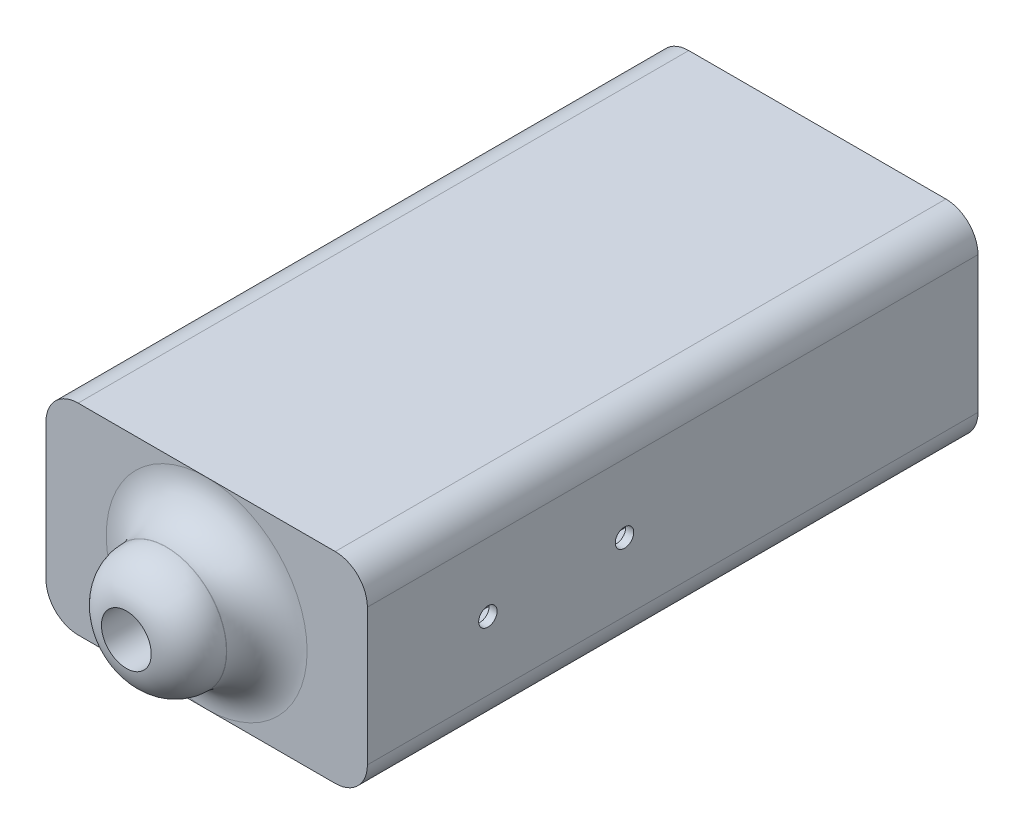
SolidWorks part; units mm, degrees
material "PLA Aero Bambu"
ref_plane "Front Plane" through (0, 0, 0) normal (0, 0, 1) x (1, 0, 0)
ref_plane "Top Plane" through (0, 0, 0) normal (0, 1, 0) x (1, 0, 0)
ref_plane "Right Plane" through (0, 0, 0) normal (1, 0, 0) x (0, 0, -1)
sketch "Sketch1" plane through (0, 0, 0) normal (0, 0, 1) x (1, 0, 0)
  line L1 (-20, 12.5) -> (20, 12.5)
  line L2 (-20, 12.5) -> (-20, -12.5)
  line L3 (-20, -12.5) -> (20, -12.5)
  line L4 (20, 12.5) -> (20, -12.5)
  line L5 (-20, 12.5) -> (20, -12.5) construction
  line L6 (-20, -12.5) -> (20, 12.5) construction
  circle A0 centre (0, 0) radius 2
  point P0 (0, 0)
  dimension "D3" = 4
  dimension "D1" = 25
  dimension "D2" = 40
extrude "Boss-Extrude1" add sketch "Sketch1" against normal blind 1
sketch "Sketch2" plane through (0, 0, -1) normal (0, 0, -1) x (-1, 0, 0)
  line L0 (-20, 12.5) -> (-20, -12.5)
  line L1 (20, -12.5) -> (-20, -12.5) construction
  line L2 (-20, -12.5) -> (20, -12.5)
  line L3 (20, -12.5) -> (20, 12.5)
  line L4 (20, 12.5) -> (-20, 12.5)
  line L5 (19, 11.5) -> (-19, 11.5)
  line L6 (-19, 11.5) -> (-19, -11.5)
  line L7 (-19, -11.5) -> (19, -11.5)
  line L8 (19, -11.5) -> (19, 11.5)
  dimension "D1" = 1
extrude "Boss-Extrude2" add sketch "Sketch2" along normal blind 75
fillet "Fillet2" radius 4 8 edges at (20, 12.5, -38) (20, -12.5, -38) (-20, -12.5, -38) (-20, 12.5, -38) (-19, -11.5, -38.5) (-19, 11.5, -38.5) (19, 11.5, -38.5) (19, -11.5, -38.5)
sketch "Sketch4" plane through (0, 0, 0) normal (0, 0, 1) x (1, 0, 0)
  circle A0 centre (0, 0) radius 7.5
  circle A1 centre (0, 0) radius 3.1
  dimension "D1" = 6.2
  dimension "D2" = 15
extrude "Boss-Extrude3" add sketch "Sketch4" along normal blind 10
fillet "Fillet3" radius 5 2 edges at (7.5, 0, 0) (7.5, 0, 10)
sketch "Sketch5" plane through (20, 0, 0) normal (1, 0, 0) x (0, 0, -1)
  circle A0 centre (15, 0) radius 1.15
  circle A1 centre (32, 0) radius 1.15
  point P5 (30.5, 0)
  point P6 (0, 0)
  dimension "D1" = 2.3
  dimension "D3" = 2.3
  dimension "D2" = 15
  dimension "D4" = 17
extrude "Cut-Extrude1" cut sketch "Sketch5" against normal through all
sketch "Sketch10" plane through (0, -11.5, 0) normal (0, 1, 0) x (1, 0, 0)
  line L0 (-20, 32.5) -> (20, 32.5)
  line L1 (15, 1) -> (-15, 1) construction
  line L2 (20, 30.85) -> (20, 33.15) construction
  line L3 (-15, 76) -> (-15, 1) construction
  line L5 (-20, 33.15) -> (-20, 30.85) construction
  line L6 (-15, 47.6018) -> (7.4768, 47.6018)
  line L7 (-15, 47.6018) -> (-15, 25.1)
  line L8 (-15, 25.1) -> (7.4768, 25.1)
  line L9 (7.4768, 47.6018) -> (7.4768, 25.1)
  point P2 (13.2446, 32.5)
  line B0 (7.4768, 39.9) -> (13.2446, 39.9) construction
  line B1 (-15, 47.6018) -> (7.4768, 47.6018) construction
  line B2 (-15, 47.6018) -> (-15, 25.1) construction
  line B3 (-15, 25.1) -> (7.4768, 25.1) construction
  line B4 (7.4768, 47.6018) -> (7.4768, 25.1) construction
  line B5 (13.2446, 39.9) -> (13.2446, 25.1) construction
  line B6 (13.2446, 25.1) -> (7.4768, 25.1) construction
  line B7 (3.3268, 47.6165) -> (3.3268, 52.475) construction
  line B8 (3.3268, 52.475) -> (5.8268, 52.475) construction
  line B9 (5.8268, 52.475) -> (5.7933, 47.65) construction
  line B10 (5.8268, 25.1) -> (5.8268, 20.2604) construction
  line B11 (5.8268, 20.2604) -> (3.3268, 20.275) construction
  line B12 (3.3268, 20.275) -> (3.3268, 25.1335) construction
  line M3 (-15, 76) -> (-15, 1)
  dimension "D1" = 31.5
sketch_block_instance "Block1-1"
sketch_block "Block1"
extrude "Boss-Extrude4" add sketch "Sketch10" along normal blind 6 contours L9 L0 L8 M3 | L9 L6 L0 M3 region at (-3.7616, -11.5, -40.0509) region at (-3.7616, -11.5, -28.8)
sketch "Sketch12" plane through (0, -11.5, 0) normal (0, 1, 0) x (1, 0, 0)
  line L0 (3.3268, 52.475) -> (5.8268, 52.475) construction
  line L1 (3.3268, 47.6165) -> (0.8268, 47.6165)
  line L2 (3.3268, 47.6165) -> (3.3268, 52.475)
  line L3 (3.3268, 52.475) -> (0.8268, 52.475)
  line L4 (0.8268, 47.6165) -> (0.8268, 52.475)
  line L6 (3.3268, 25.1335) -> (0.8268, 25.1335)
  line L7 (3.3268, 25.1335) -> (3.3268, 20.275)
  line L8 (3.3268, 20.275) -> (0.8268, 20.2896)
  line L9 (0.8268, 25.1335) -> (0.8268, 20.2896)
  line L11 (5.8268, 20.2604) -> (3.3268, 20.275) construction
  point P5 (2.0768, 52.475)
  dimension "D1" = 0
  dimension "D2" = 2.5
  dimension "D3" = 2.5
extrude "Boss-Extrude5" add sketch "Sketch12" along normal blind 15
sketch "Sketch13" plane through (3.3268, 0, 0) normal (1, 0, 0) x (0, 0, -1)
  line L0 (47.6018, -5.5) -> (25.1, -5.5) construction
  line L1 (20.275, 3.5) -> (25.1335, 3.5) construction
  line L2 (47.6165, 3.5) -> (52.475, 3.5) construction
  circle A0 centre (22.7042, 0) radius 1.35
  circle A1 centre (50.0458, 0) radius 1.35
  point P6 (0, 0)
  point P7 (50.0458, 3.5)
  point P11 (22.7042, 3.5)
  dimension "D2" = 2.7
  dimension "D3" = 2.7
  dimension "D1" = 5.5
extrude "Cut-Extrude3" cut sketch "Sketch13" against normal blind 12
sketch "Sketch15" plane through (0, -11.5, 0) normal (0, 1, 0) x (1, 0, 0)
  line L0 (19, 76) -> (19, 1) construction
  line L1 (9, 18) -> (14, 18)
  line L2 (9, 18) -> (9, 12)
  line L3 (9, 12) -> (14, 12)
  line L4 (14, 18) -> (14, 12)
  line L5 (9, 12) -> (14, 18) construction
  line L6 (14, 12) -> (9, 18) construction
  line L8 (15, 1) -> (-15, 1) construction
  point P6 (11.5, 15)
  point P7 (0, 0)
  point P8 (0, 0)
  dimension "D1" = 5
  dimension "D2" = 6
  dimension "D3" = 5
  dimension "D4" = 14
extrude "Boss-Extrude6" add sketch "Sketch15" along normal blind 14
sketch "Sketch16" plane through (14, 0, 0) normal (1, 0, 0) x (0, 0, -1)
  circle A0 centre (15, 0) radius 1.25
extrude "Cut-Extrude4" cut sketch "Sketch16" against normal blind 5
